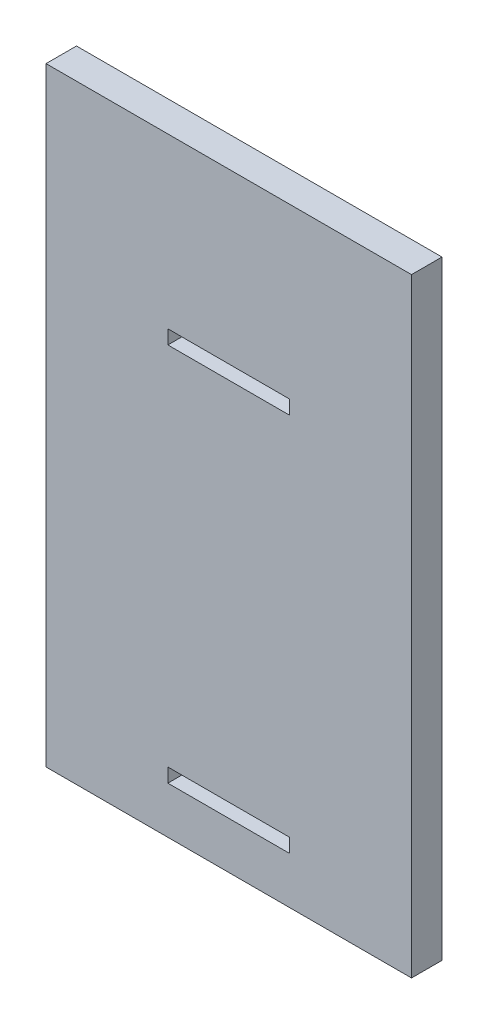
SolidWorks part; units mm, degrees
material "PBT General Purpose"
ref_plane "Front Plane" through (0, 0, 0) normal (0, 0, 1) x (1, 0, 0)
ref_plane "Top Plane" through (0, 0, 0) normal (0, 1, 0) x (1, 0, 0)
ref_plane "Right Plane" through (0, 0, 0) normal (1, 0, 0) x (0, 0, -1)
sketch "frame_outline" plane through (0, 0, 0) normal (0, 0, 1) x (1, 0, 0)
  line L124 (0, 0) -> (3, 0)
  line L125 (0, 0) -> (0, 5)
  line L126 (0, 5) -> (3, 5)
  line L127 (3, 0) -> (3, 5)
  line L128 (1, 3.615) -> (2, 3.615)
  line L129 (1, 3.615) -> (1, 3.5)
  line L130 (1, 3.5) -> (2, 3.5)
  line L131 (2, 3.615) -> (2, 3.5)
  line L132 (1, 0.5) -> (2, 0.5)
  line L133 (1, 0.5) -> (1, 0.385)
  line L134 (1, 0.385) -> (2, 0.385)
  line L135 (2, 0.5) -> (2, 0.385)
  point P12 (1.5, 0.385)
  point P13 (1.5, 0)
  dimension "D1" = 1
  dimension "D2" = 3
  dimension "D3" = 0.115
  dimension "D4" = 5
  dimension "D5" = 3
  dimension "D6" = 1.5
extrude "Boss-Extrude1" add sketch "frame_outline" along normal mid plane 0.25
equation "\"t\"= 0.25'thickness of the sheets"
equation "\"t_cf\" = 0.115'thickness of single carbon fiber layer"
equation "\"t_kapton\" = 0.025'thickness of single Kapton flex layer"
equation "\"t_fr4\" = 0.1'thickness of FR4 with copper layer"
equation "\"joint_flex\"= 0.1'Width of flextures gap"
equation "\"joint_flex_eff\"= 0.02'Width of flecture after castelation"
equation "\"joint_fold\"= 0.2'Width of folding joints for 90deg fold"
equation "\"gap_tolerance\"= 0.002'Width to have interfecence fit between carbon fiber inserts"
equation "\"assemble_angle\"= 90'Angle of assembly parts"
equation "\"D1@Boss-Extrude1\"=\"t\""
equation "\"link_lift\"= 0.5'Actuation linkage amplification for the lift motion"
equation "\"link_swing\"= 0.45'Actuation linkage amplification for the swing motion"
